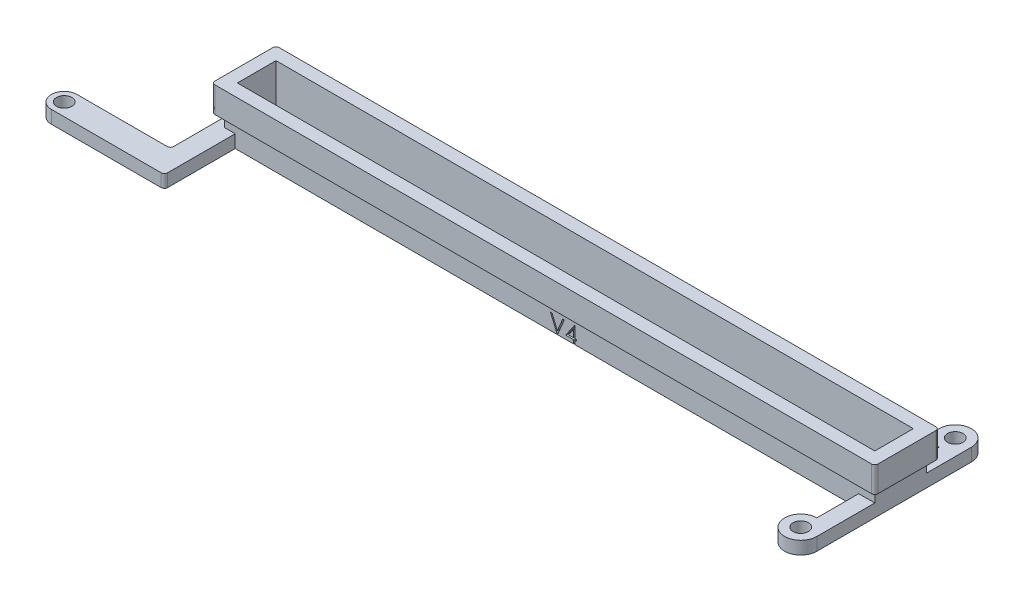
SolidWorks part; units mm, degrees
ref_plane "Front Plane" through (0, 0, 0) normal (0, 0, 1) x (1, 0, 0)
ref_plane "Top Plane" through (0, 0, 0) normal (0, 1, 0) x (1, 0, 0)
ref_plane "Right Plane" through (0, 0, 0) normal (1, 0, 0) x (0, 0, -1)
sketch "Sketch1" plane through (0, 0, 0) normal (0, 1, 0) x (1, 0, 0)
  line L0 (-50.5, 4) -> (-50.5, -4)
  line L1 (-49.5, 3) -> (49.5, 3)
  line L2 (-49.5, 3) -> (-49.5, -3)
  line L3 (-49.5, -3) -> (49.5, -3)
  line L4 (49.5, 3) -> (49.5, -3)
  line L5 (-49.5, 3) -> (49.5, -3) construction
  line L6 (-49.5, -3) -> (49.5, 3) construction
  line L7 (-50.5, -4) -> (50.5, -4)
  line L8 (50.5, 4) -> (50.5, -4)
  line L9 (-50.5, 4) -> (50.5, 4)
  point P0 (0, 0)
  dimension "D1" = 6
  dimension "D2" = 99
  dimension "D3" = 1
extrude "Boss-Extrude1" add sketch "Sketch1" along normal blind 10
sketch "Sketch2" plane through (0, 0, 0) normal (0, -1, 0) x (1, 0, 0)
  line L0 (0, 0) -> (74.3491, 0) construction
  line L1 (48, 0) -> (48, 10.5) construction
  line L2 (50.5, 4) -> (50.5, -4) construction
  line L4 (50.5, 4) -> (67.4224, 4) construction
  line L5 (50.5, -4) -> (69.4178, -4) construction
  line L7 (48, 4) -> (50.5, 4)
  line L9 (48, -4) -> (50.5, -4)
  line L11 (48, 0) -> (48, -8.5) construction
  line L15 (50.5, 4) -> (50.5, 13)
  line L16 (50.5, 13) -> (50, 13) construction
  line L17 (50.5, -4) -> (50.5, -11)
  line L18 (50.5, -11) -> (50, -11) construction
  line L19 (48, 10.5) -> (48, 4)
  line L20 (48, -8.5) -> (48, -4)
  line L21 (-50.5, 4) -> (-50.5, 13) construction
  line L22 (-50.5, 13) -> (-64.4, 13) construction
  line L23 (-66.4, 15) -> (-48.8351, 15)
  line L24 (-48.8351, 15) -> (-48.8351, 4)
  line L25 (-50.5, 4) -> (50.5, 4) construction
  line L26 (-66.4, 11) -> (-51.9017, 11)
  line L27 (-50.5, -4) -> (-59.3527, -4) construction
  line L28 (-51.9017, 11) -> (-51.9017, -4)
  line L29 (-51.9017, -4) -> (-50.5, -4)
  line L30 (-50.5, -4) -> (-50.5, 4)
  line L31 (-50.5, 4) -> (-48.8351, 4)
  line L32 (-64.4, 13) -> (-65.2, 13) construction
  line L33 (-65.2, 13) -> (-66.4, 13) construction
  line L34 (48, 10.5) -> (48, 11) construction
  line L35 (48, 11) -> (48, 13) construction
  line L36 (48, 11) -> (48, 10.5) construction
  line L37 (48, -8.5) -> (48, -9) construction
  line L38 (48, -9) -> (48, -11) construction
  line L39 (48, -9) -> (48, -8.5) construction
  circle A0 centre (48, 13) radius 1.2
  circle A4 centre (48, -11) radius 1.2
  arc A5 (50.5, -11) -> (48, -8.5) centre (48, -11) ccw construction
  arc A8 (48, 10.5) -> (50.5, 13) centre (48, 13) ccw construction
  circle A10 centre (-66.4, 13) radius 1.2
  arc A11 (-66.4, 15) -> (-66.4, 11) centre (-66.4, 13) ccw
  arc A12 (-64.4, 13) -> (-66.4, 15) centre (-66.4, 13) ccw construction
  arc A13 (-66.4, 11) -> (-64.4, 13) centre (-66.4, 13) ccw construction
  arc A14 (50.5, 13) -> (48, 10.5) centre (48, 13) ccw
  arc A15 (48, -8.5) -> (50.5, -11) centre (48, -11) ccw
  dimension "D3" = 2.4
  dimension "D9" = 2.4
  dimension "D10" = 4
  dimension "D1" = 2.5
  dimension "D2" = 13
  dimension "D5" = 11
  dimension "D7" = 9
  dimension "D8" = 15.9
extrude "Boss-Extrude2" add sketch "Sketch2" against normal blind 2
sketch "Sketch3" plane through (0, 10, 0) normal (0, 1, 0) x (1, 0, 0)
  line L0 (51.5, 5) -> (-51.5, 5)
  line L1 (-51.5, 5) -> (-51.5, -5)
  line L2 (-51.5, -5) -> (51.5, -5)
  line L3 (51.5, -5) -> (51.5, 5)
  line L4 (50.5, 4) -> (-50.5, 4)
  line L5 (-50.5, 4) -> (-50.5, -4)
  line L6 (-50.5, -4) -> (50.5, -4)
  line L7 (50.5, -4) -> (50.5, 4)
  line L8 (50.5, 4) -> (-50.5, 4)
  line L9 (-50.5, 4) -> (-50.5, -4)
  line L10 (-50.5, -4) -> (50.5, -4)
  line L11 (50.5, -4) -> (50.5, 4)
  dimension "D1" = 0
  dimension "D2" = 1
extrude "Boss-Extrude3" add sketch "Sketch3" against normal blind 6
fillet "Fillet4" radius 1 1 edges at (0, 4, -4)
fillet "Fillet5" radius 1 1 edges at (0, 4, 4)
fillet "Fillet6" radius 1 1 edges at (50.5, 4, 0)
fillet "Fillet7" radius 1 1 edges at (-50.5, 4, 0)
fillet "Fillet8" radius 0.5 2 edges at (-48.8351, 1, 15) (-51.9017, 1, 11)
fillet "Fillet9" radius 0.5 4 edges at (51.5, 7, -5) (51.5, 7, 5) (-51.5, 7, 5) (-51.5, 7, -5)
sketch "Sketch4" plane through (0, 10, 0) normal (0, 1, 0) x (1, 0, 0)
  line L4 (51.5, -4.5) -> (51.5, 4.5)
  line L5 (51, 5) -> (-51, 5)
  line L6 (-51.5, 4.5) -> (-51.5, -4.5)
  line L7 (-51, -5) -> (51, -5)
  line L8 (51.5, -4.5) -> (51.5, 4.5)
  line L9 (51, 5) -> (-51, 5)
  line L10 (-51.5, 4.5) -> (-51.5, -4.5)
  line L11 (-51, -5) -> (51, -5)
  arc A4 (51.5, 4.5) -> (51, 5) centre (51, 4.5) ccw
  arc A5 (-51, 5) -> (-51.5, 4.5) centre (-51, 4.5) ccw
  arc A6 (-51.5, -4.5) -> (-51, -5) centre (-51, -4.5) ccw
  arc A7 (51, -5) -> (51.5, -4.5) centre (51, -4.5) ccw
  arc A8 (51.5, 4.5) -> (51, 5) centre (51, 4.5) ccw
  arc A9 (-51, 5) -> (-51.5, 4.5) centre (-51, 4.5) ccw
  arc A10 (-51.5, -4.5) -> (-51, -5) centre (-51, -4.5) ccw
  arc A11 (51, -5) -> (51.5, -4.5) centre (51, -4.5) ccw
  dimension "D1" = 0
extrude "Cut-Extrude1" cut sketch "Sketch4" against normal blind 2
sketch "Sketch5" plane through (0, 0, 4) normal (0, 0, 1) x (1, 0, 0)
  text T0 "V4\r\n" font "Century Gothic" height 2.5
extrude "Cut-Extrude2" cut sketch "Sketch5" against normal blind 0.5
